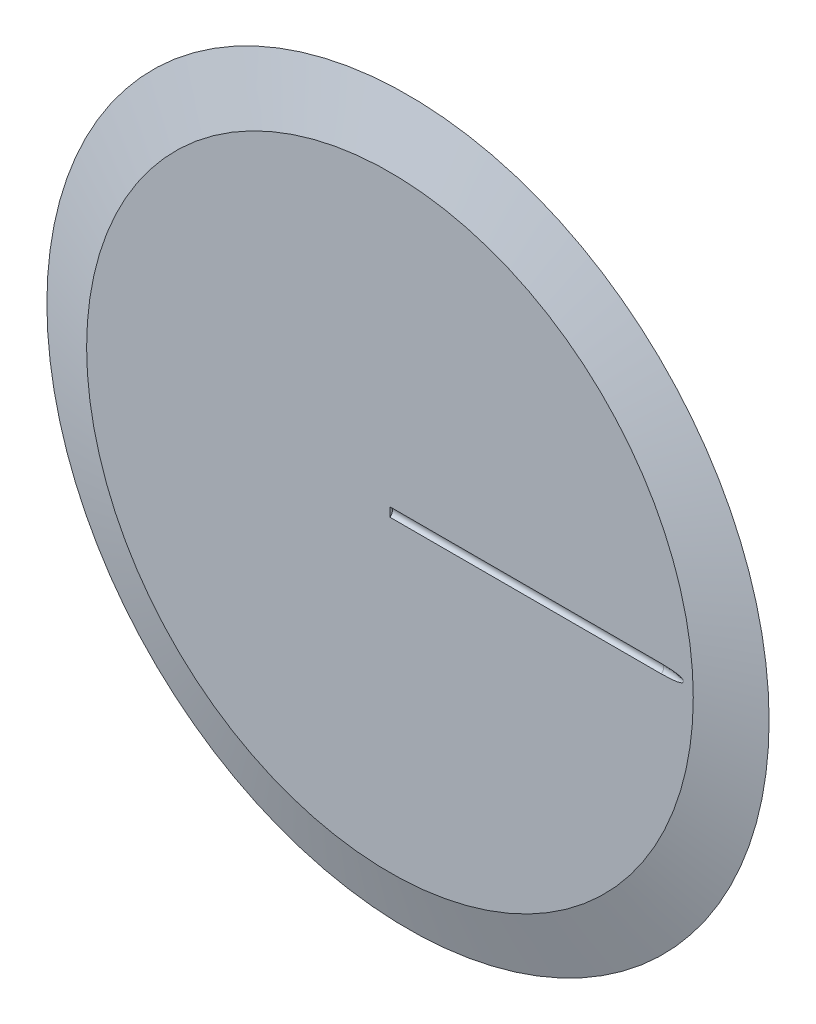
SolidWorks part; units mm, degrees
ref_plane "Front Plane" through (0, 0, 0) normal (0, 0, 1) x (1, 0, 0)
ref_plane "Top Plane" through (0, 0, 0) normal (0, 1, 0) x (1, 0, 0)
ref_plane "Right Plane" through (0, 0, 0) normal (1, 0, 0) x (0, 0, -1)
sketch "Blade Base" plane through (0, 0, 0) normal (0, 0, 1) x (1, 0, 0)
  circle A0 centre (0, 0) radius 63.5
  dimension "D1" = 127
extrude "Blade Base Extrude" add sketch "Blade Base" along normal blind 3.175 contours A0
chamfer "Blade Chamfer" distance 3.175 distance2 10.16 1 edges at (63.5, 0, 3.175) first distance on face at (63.5, 0, 3.175)
sketch "Centerlines" plane through (0, 0, 0) normal (0, 0, 1) x (1, 0, 0)
  line L0 (-72.8006, 0) -> (71.3256, 0) construction
  line L1 (0, 68.0779) -> (0, -68.2726) construction
sketch "Sluice Cross Section" plane through (0, 0, 0) normal (1, 0, 0) x (0, 0, -1)
  line L1 (-3.175, 0.7937) -> (-3.175, 2.3812)
  line L2 (-3.175, 53.34) -> (-3.175, -53.34) construction
  arc A0 (-3.175, 2.3812) -> (-3.175, 0.7937) centre (-3.6818, 1.5875) cw
  point P8 (0, 0)
  point P9 (-3.175, 2.09)
  point P10 (-3.175, 2.3962)
  dimension "D2" = 0.7937
  dimension "D3" = 1.5875
ref_plane "Sluice Path Plane" through (0, 1.5875, 0) normal (0, 1, 0) x (1, 0, 0)
sketch "Sluice Path" plane through (0, 1.5875, 0) normal (0, 1, 0) x (1, 0, 0)
  line L0 (0, -4.7581) -> (0, 1.346) construction
  line L1 (47.704, -3.175) -> (-47.704, -3.175)
  line L2 (-53.34, -3.175) -> (53.34, -3.175) construction
  spline S0 degree 2 poles (-47.704, -3.175) (-49.7116, -3.1769) (-51.6643, -3.6268) knots 0 0 0 1 1 1
  spline S1 degree 2 poles (47.704, -3.175) (49.7116, -3.1769) (51.6643, -3.6268) knots 0 0 0 1 1 1
  point P10 (0, -3.175)
sweep "Cut-Sweep1" cut profiles "Sluice Cross Section" path "Sluice Path"
